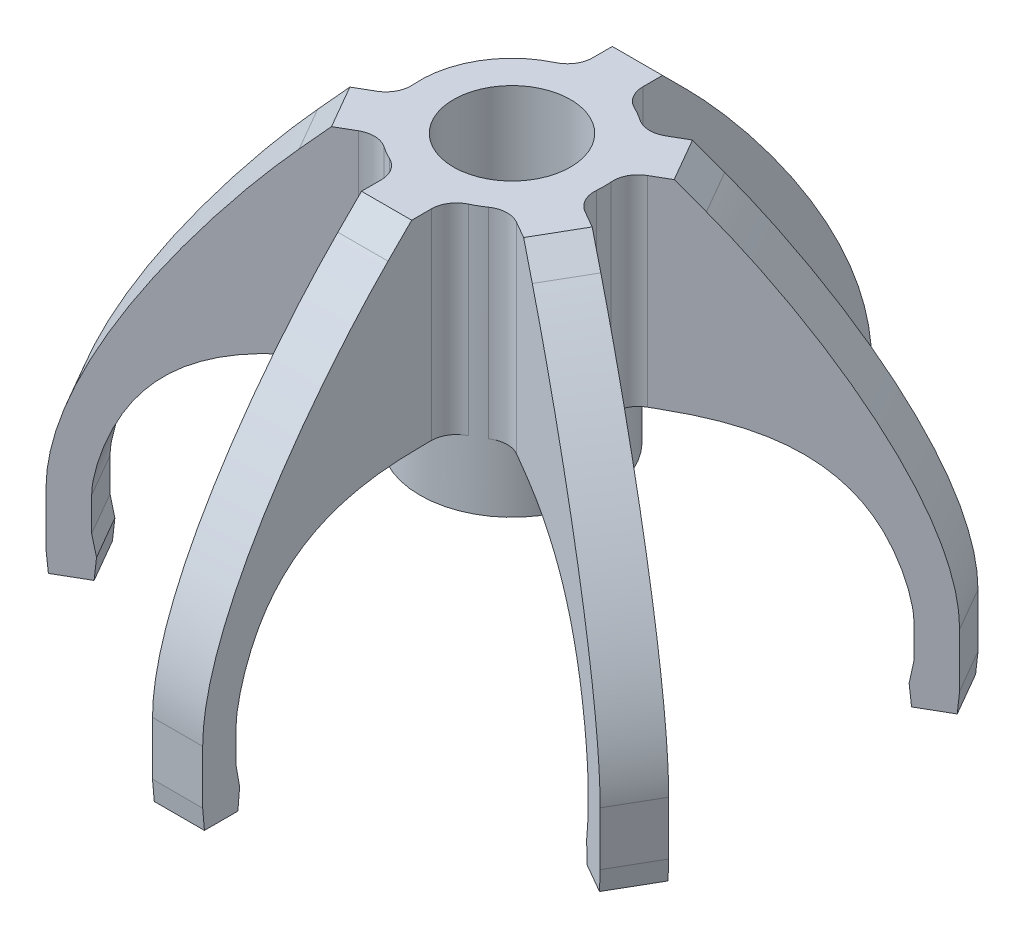
SolidWorks part; units mm, degrees
ref_plane "Front Plane" through (0, 0, 0) normal (0, 0, 1) x (1, 0, 0)
ref_plane "Top Plane" through (0, 0, 0) normal (0, 1, 0) x (1, 0, 0)
ref_plane "Right Plane" through (0, 0, 0) normal (1, 0, 0) x (0, 0, -1)
sketch "Sketch1" plane through (0, 0, 0) normal (0, 1, 0) x (1, 0, 0)
  circle A0 centre (0, 0) radius 1.25
  circle A1 centre (0, 0) radius 3.5 construction
  circle A2 centre (0, 0) radius 5.5
  dimension "D1" = 2.5
  dimension "D2" = 7
  dimension "D3" = 2
extrude "Boss-Extrude1" add sketch "Sketch1" along normal blind 16
sketch "Sketch2" plane through (0, 0, 0) normal (1, 0, 0) x (0, 0, -1)
  line L0 (-19, -5) -> (19, -5) construction
  line L1 (-5.5, 0) -> (5.5, 0) construction
  line L3 (18, -5) -> (20, -5)
  line L4 (5.5, 16) -> (-5.5, 16) construction
  line L6 (5.5, 16) -> (1.25, 16)
  line L7 (1.25, 16) -> (1.25, 4)
  line L8 (1.25, 4) -> (6.7057, 4)
  line L9 (7.5, 16) -> (8.9142, 14.5858)
  line L11 (5.5, 16) -> (7.5, 16)
  spline S0 degree 3 poles (6.7057, 4) (10.5222, 4) (16.0212, 3.2573) (18, -4.0057) (18, -5) knots 0 0 0 0 0.785491 1 1 1 1
  spline S1 degree 3 poles (8.9142, 14.5858) (13.0743, 10.4257) (20, 1.4618) (20, -5) knots 0.147346 0.147346 0.147346 0.147346 1 1 1 1
  spline S2 degree 3 poles (5.5, 16) (7.3851, 16) (8.1598, 15.3395) (8.8783, 14.6217) (8.9142, 14.5858) knots 0 0 0 0 0.139979 0.147346 0.147346 0.147346 0.147346 construction
  point P3 (0, -5)
  point P7 (-19, -5)
  point P8 (19, -5)
  point P11 (19, -5)
  point P13 (7.2936, 16.0728)
  point P15 (17.012, -1.1955)
  point P19 (7.0916, 16)
  point P20 (0, 0)
  point P24 (9.7687, 13.7313)
  point P25 (9.351, 14.149)
  point P28 (18.2298, -2.0387)
  point P29 (0, 0)
  point P30 (16.8051, -1.5631)
  point P31 (16.6082, -1.0154)
  point P32 (16.5478, -1.7605)
  point P33 (17.4061, -1.6461)
  point P34 (16.9891, -1.1897)
  dimension "D1" = 38
  dimension "D2" = 5
  dimension "D3" = 2
  dimension "D4" = 12
  dimension "D5" = 45
  dimension "D6" = 2
  dimension "D7" = 2
extrude "Boss-Extrude2" add sketch "Sketch2" along normal blind 1.5 and the other way blind 1.5
sketch "Sketch8" plane through (1.5, 0, 0) normal (1, 0, 0) x (0, 0, -1)
  line L0 (18, -7) -> (17.7884, -8.2)
  line L1 (18, -5) -> (20, -5)
  line L2 (18, -5) -> (18, -7)
  line L3 (18, -7) -> (20, -7) construction
  line L4 (20, -5) -> (20, -7)
  line L5 (17.7884, -8.2) -> (20, -8.2) construction
  line L6 (20, -8.2) -> (20, -7)
  line L7 (17.7884, -8.2) -> (17.8942, -9.4093)
  line L8 (17.8942, -9.4093) -> (19.8942, -9.4093)
  line L9 (19.8942, -9.4093) -> (20, -8.2)
  point P5 (0, 0)
  dimension "D1" = 2
  dimension "D2" = 10
  dimension "D4" = 1.2
  dimension "D5" = 5
  dimension "D6" = 5
extrude "Boss-Extrude3" add sketch "Sketch8" against normal up to surface (3 mm away) up to face at (-1.5, 5.6133, -10.2284)
pattern_circular "CirPattern1" count 5 every 60 about axis through (0, 16, 0) along (0, -1, 0) of "Boss-Extrude2", "Boss-Extrude3"
fillet "Fillet1" radius 1.5 10 edges at (3.8326, 10, 3.9448) (1.5, 10, 5.2915) (-1.5, 10, 5.2915) (-3.8326, 10, 3.9448) (-5.3326, 10, 1.3467) (-1.5, 10, -5.2915) (3.8326, 10, -3.9448) (1.5, 10, -5.2915) (5.3326, 10, 1.3467) (5.3326, 10, -1.3467)
sketch "Sketch6" plane through (0, 16, 0) normal (0, 1, 0) x (1, 0, 0)
  circle A0 centre (0, 0) radius 3.5
  dimension "D1" = 7
extrude "Cut-Extrude1" cut sketch "Sketch6" against normal offset from surface (15.2 mm away) 0.8 up to face at (0, 0, 5.5)
